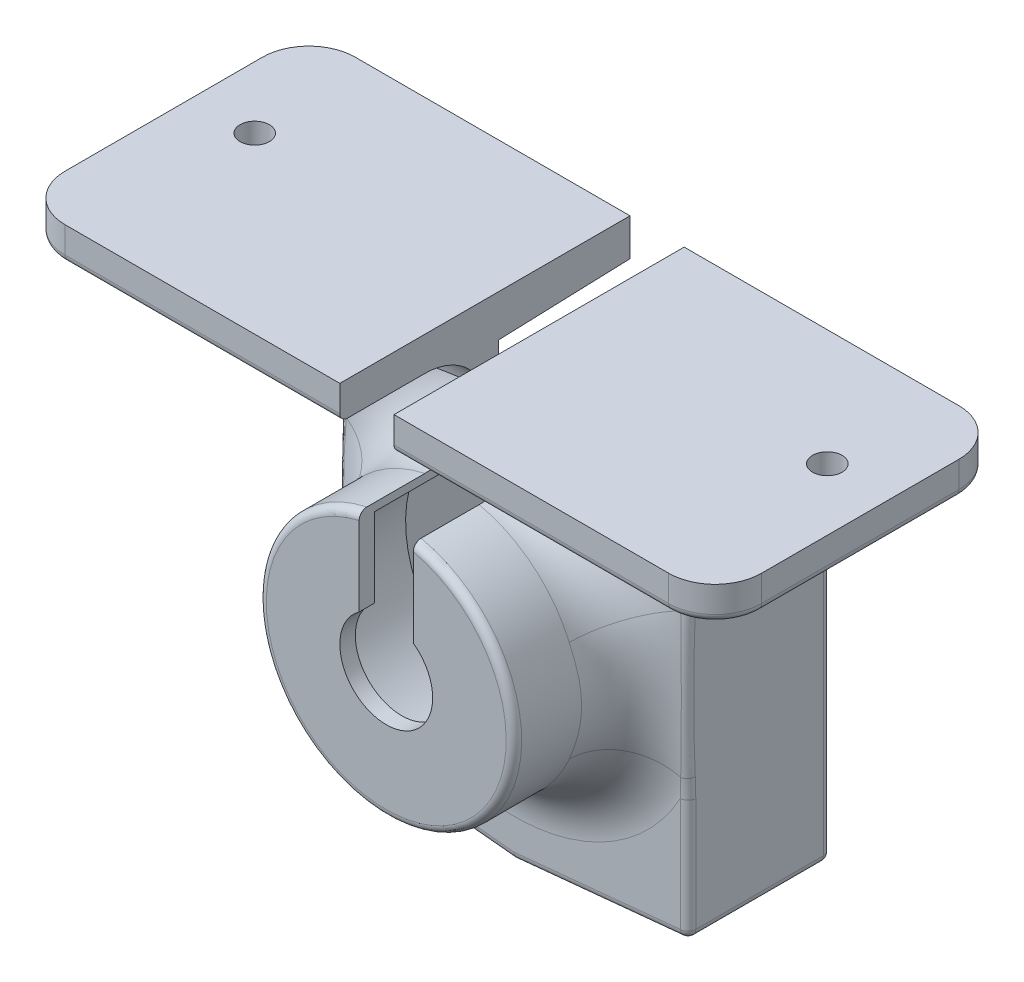
SolidWorks part; units mm, degrees
note: The reader was unsure of these and kept them because the rebuilt part matched: shared geometry of "Skizze1<6>", "Skizze1<8>", "Skizze1<7>".
ref_plane "Ebene vorne" through (0, 0, 0) normal (0, 0, 1) x (1, 0, 0)
ref_plane "Ebene oben" through (0, 0, 0) normal (0, 1, 0) x (1, 0, 0)
ref_plane "Ebene rechts" through (0, 0, 0) normal (1, 0, 0) x (0, 0, -1)
sketch "Skizze1" plane through (0, 0, 0) normal (0, 0, 1) x (1, 0, 0)
  line L4 (0, 42.4636) -> (0, -101.4826) construction
  line L5 (11.2636, -3.1084) -> (20.5, -4.0095)
  line L6 (20.5, -4.0095) -> (20.5, -55.0095)
  line L7 (20.5, -29.5095) -> (-20.5, -29.5095) construction
  line L8 (11.2636, -55.9106) -> (20.5, -55.0095)
  line L9 (-11.2636, -55.9106) -> (-20.5, -55.0095)
  line L10 (-20.5, -4.0095) -> (-20.5, -55.0095)
  line L11 (-11.2636, -3.1084) -> (-20.5, -4.0095)
  line L12 (0, 0) -> (122.9392, 0) construction
  line L13 (0, 0) -> (22.5, -2.1951)
  line L14 (22.5, -2.1951) -> (22.5, -56.8239)
  line L15 (0, -59.019) -> (22.5, -56.8239)
  line L16 (0, -59.019) -> (-22.5, -56.8239)
  line L17 (-22.5, -2.1951) -> (-22.5, -56.8239)
  line L18 (0, 0) -> (-22.5, -2.1951)
  line L19 (0, -2.0095) -> (20.5, -4.0095) construction
  line L20 (0, -2.0095) -> (-20.5, -4.0095) construction
  line L21 (0, -57.0095) -> (20.5, -55.0095) construction
  line L22 (0, -57.0095) -> (-20.5, -55.0095) construction
  line L24 (-45, -2.1951) -> (45, -2.1951)
  line L25 (-45, -2.1951) -> (-45, 2.1951)
  line L26 (-45, 2.1951) -> (45, 2.1951)
  line L27 (45, -2.1951) -> (45, 2.1951)
  line L28 (-45, -2.1951) -> (45, 2.1951) construction
  line L29 (-45, 2.1951) -> (45, -2.1951) construction
  arc A0 (11.2636, -3.1084) -> (-11.2636, -3.1084) centre (0, -118.5602) ccw
  arc A1 (11.2636, -55.9106) -> (-11.2636, -55.9106) centre (0, 59.5412) cw
  circle A2 centre (0, -29.5095) radius 15.5
  point P4 (0, -29.5095)
  point P33 (0, -2.0095)
  point P37 (0, -57.0095)
  dimension "D4" = 116
  dimension "D6" = 116
  dimension "D8" = 31
  dimension "D1" = 55
  dimension "D2" = 41
  dimension "D3" = 51
  dimension "D5" = 2
  dimension "D7" = 90
extrude "Aufsatz-Linear austragen1" add sketch "Skizze1" against normal blind 17
sketch "Skizze4" plane through (0, 0, -17) normal (0, 0, -1) x (-1, 0, 0)
  line L0 (11.2636, -3.1084) -> (20.5, -4.0095) construction
  line L1 (-11.2636, -3.1084) -> (-20.5, -4.0095) construction
  line L2 (-20.5, -4.0095) -> (-20.5, -55.0095) construction
  line L3 (-11.2636, -55.9106) -> (-20.5, -55.0095) construction
  line L4 (11.2636, -55.9106) -> (20.5, -55.0095) construction
  line L5 (20.5, -4.0095) -> (20.5, -55.0095) construction
  line L6 (11.2636, -3.1084) -> (20.5, -4.0095)
  line L7 (-11.2636, -3.1084) -> (-20.5, -4.0095)
  line L8 (-20.5, -4.0095) -> (-20.5, -55.0095)
  line L9 (-11.2636, -55.9106) -> (-20.5, -55.0095)
  line L10 (11.2636, -55.9106) -> (20.5, -55.0095)
  line L11 (20.5, -4.0095) -> (20.5, -55.0095)
  arc A0 (11.2636, -3.1084) -> (-11.2636, -3.1084) centre (0, -118.5602) ccw construction
  arc A1 (-11.2636, -55.9106) -> (11.2636, -55.9106) centre (0, 59.5412) ccw construction
  arc A2 (11.2636, -3.1084) -> (-11.2636, -3.1084) centre (0, -118.5602) ccw
  arc A3 (-11.2636, -55.9106) -> (11.2636, -55.9106) centre (0, 59.5412) ccw
extrude "Schnitt-Linear austragen5" cut sketch "Skizze4" against normal up to surface (17 mm away) draft 2
extrude "Aufsatz-Linear austragen4" add sketch "Skizze1<6>" along normal blind 1.5 contours L24 L17 L16 L15 L14 L8 A1 L9 L10 L11 A0 L5 L6 | A1 L8 L6 L5 A0 L11 L10 L9 A2
sketch "Skizze1<6>" plane through (0, 0, 0) normal (0, 0, 1) x (1, 0, 0) same geometry as "Skizze1"
extrude "Linear-Austragen-Dünn1" add sketch "Skizze1<8>" along normal blind 16 thin contours A2
sketch "Skizze1<8>" plane through (0, 0, 0) normal (0, 0, 1) x (1, 0, 0) same geometry as "Skizze1"
sketch "Skizze6" plane through (0, 0, 16) normal (0, 0, 1) x (1, 0, 0)
  circle A0 centre (0, -29.5095) radius 16.5
  circle A1 centre (0, -29.5095) radius 16.5 construction
  point P4 (-3.4854, -28.4774)
extrude "Aufsatz-Linear austragen6" add sketch "Skizze6" along normal blind 2
extrude "Aufsatz-Linear austragen5" add sketch "Skizze1<7>" along normal blind 20.5 contours L24 L27 L26 L25 L18 L13 | L18 L24 L13
sketch "Skizze1<7>" plane through (0, 0, 0) normal (0, 0, 1) x (1, 0, 0) same geometry as "Skizze1"
fillet "Verrundung1" radius 8 4 edges at (22.5, -2.1951, -7.75) (-22.5, -2.1951, -7.75) (16.5, -29.5095, 1.5) (0, -2.1951, 1.5)
fillet "Verrundung2" radius 6 4 edges at (45, 0, -17) (-45, 0, -17) (45, 0, 20.5) (-45, 0, 20.5)
fillet "Verrundung3" radius 1 28 edges at (-22.5, -33.5095, -17) (-24.8431, -4.5383, -17) (-34.75, -2.1951, -17) (-43.2426, -2.1951, -15.2426) (-45, -2.1951, 1.75) (-43.2426, -2.1951, 18.7426) (22.5, -33.5095, -17) (24.8431, -4.5383, -17) (34.75, -2.1951, -17) (43.2426, -2.1951, -15.2426) (45, -2.1951, 1.75) (43.2426, -2.1951, 18.7426) (11.25, -57.9214, -17) (-11.25, -57.9214, -17) (0, -2.1951, 20.5) (22.5, -56.8239, -7.75) (-22.5, -56.8239, -7.75) (-24.8431, -4.5383, 3.8431) (-22.5, -15.0046, 1.5) (-22.5, -29.5095, 1.5) (24.8431, -4.5383, 3.8431) (22.5, -15.0046, 1.5) (22.5, -29.5095, 1.5) (16.5, -29.5095, 18) (-22.5, -48.0144, 1.5) (-11.25, -57.9214, 1.5) (11.25, -57.9214, 1.5) (22.5, -48.0144, 1.5)
hole_wizard "Ø3.8 (3.8) Durchmesser Bohrung1" positions "3D-Skizze1" profile "Skizze3" hole size "Ø3.8" standard "ISO" end condition through all
sketch3d "3D-Skizze1"
  point P0 (-37, -2.1951, -2)
  point P26 (37, -2.1951, -2)
  dimension "D1" = 8
  dimension "D2" = 15
sketch "Skizze3" plane through (-37, -2.1951, -2) normal (1, 0, 0) x (0, 0, -1)
  line L0 (0, 0) -> (0, 4.3902)
  line L1 (0, 4.3902) -> (1.9, 4.3902)
  line L2 (1.9, 4.3902) -> (1.9, 0)
  line L5 (1.9, 0) -> (0, 0)
  line L11 (0, -6.35) -> (0, 107.95) construction
  dimension "Bohrerdurchmesser" = 3.8
  dimension "Bohrungstiefe" = 4.3902
sketch "Skizze7" plane through (0, 0, 0) normal (0, 0, 1) x (1, 0, 0)
  line L0 (0, 42.4636) -> (0, -101.4826) construction
  line L2 (-3.5, -24.6361) -> (-3.5, 2.1951)
  line L3 (-3.5, 2.1951) -> (3.5, 2.1951)
  line L4 (3.5, -24.6361) -> (3.5, 2.1951)
  line L5 (-3.5, -24.6361) -> (3.5, 2.1951) construction
  line L6 (-3.5, 2.1951) -> (3.5, -24.6361) construction
  line L7 (-45, 2.1951) -> (45, 2.1951) construction
  arc A0 (-3.5, -24.6361) -> (3.5, -24.6361) centre (0, -29.5095) ccw
  point P3 (0, -11.2205)
  point P12 (2.5411, -25.9787)
  dimension "D1" = 7
  dimension "D2" = 12
extrude "Schnitt-Linear austragen6" cut sketch "Skizze7" against normal through all both and the other way through all
